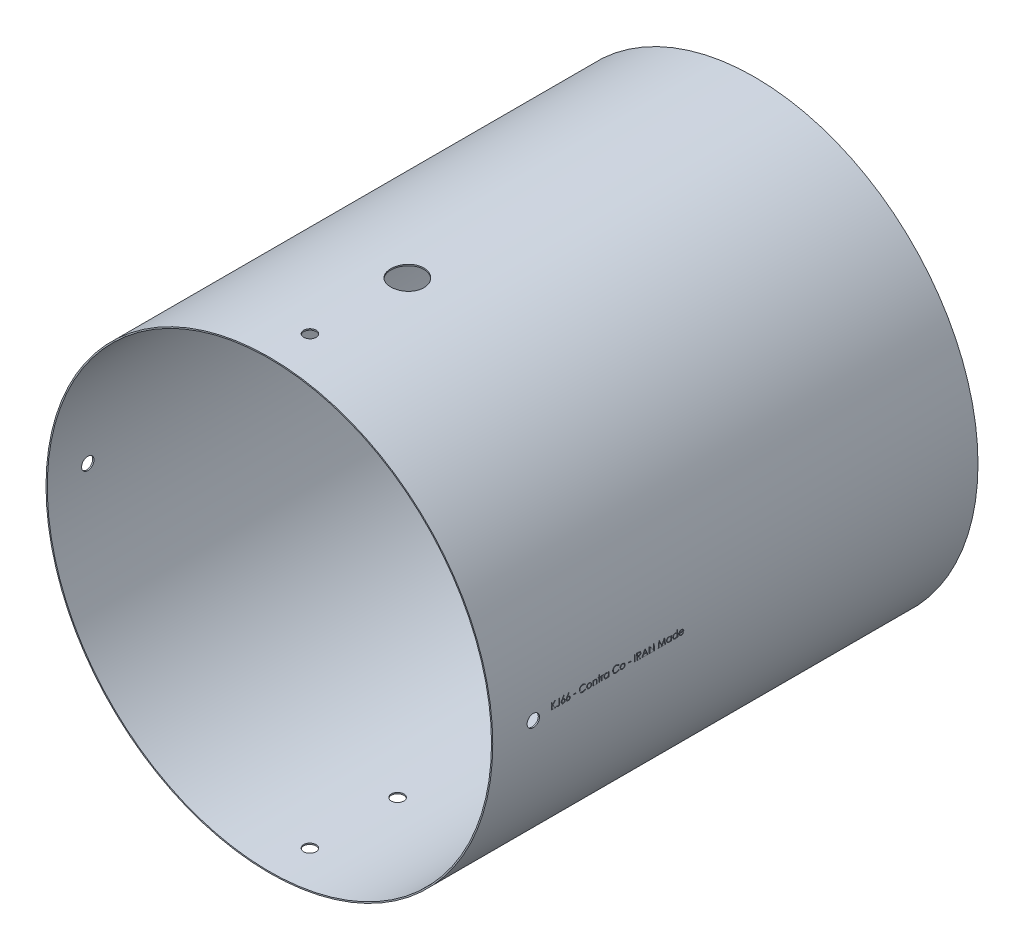
SolidWorks part; units mm, degrees
material "Chrome Stainless Steel"
ref_plane "Front Plane" through (0, 0, 0) normal (0, 0, 1) x (1, 0, 0)
ref_plane "Top Plane" through (0, 0, 0) normal (0, 1, 0) x (1, 0, 0)
ref_plane "Right Plane" through (0, 0, 0) normal (1, 0, 0) x (0, 0, -1)
sketch "Sketch1" plane through (0, 0, 0) normal (0, 1, 0) x (1, 0, 0)
  line L0 (-34.2692, 117.8) -> (-34.2692, 117.5)
  line L1 (-54, 0.4998) -> (-54, 112.5)
  line L2 (-34.2692, 117.5) -> (-53.7, 117.5)
  line L3 (-53.7, 112.5) -> (-53.7, 0.5)
  line L4 (-53.7, 117.5) -> (-53.7, 112.5)
  line L5 (-54, 0.4998) -> (-53.7, 0.5)
  line L6 (0, 0) -> (0, 62.8009) construction
  line L7 (-54, 112.5) -> (-54, 117.8)
  line L8 (-54, 117.8) -> (-34.2692, 117.8)
  point P1 (0, 0)
  point P5 (0, 0)
  point P15 (-54, 117.8)
  point P17 (-34.2692, 117.5)
  point P18 (-34.2692, 117.8)
revolve "Revolve1" add sketch "Sketch1" angle 360 about L6
ref_plane "Plane1" through (53.75, 0, 0) normal (1, 0, 0) x (0, 0, -1)
sketch "Sketch3" plane through (53.75, 0, 0) normal (1, 0, 0) x (0, 0, -1)
  circle A0 centre (10.3, 0) radius 1.5
  point P6 (10.3, 0)
ref_plane "Plane2" through (0, -53.75, 0) normal (0, 1, 0) x (1, 0, 0)
sketch "Sketch5" plane through (0, -53.75, 0) normal (0, 1, 0) x (1, 0, 0)
  circle A0 centre (0, 31.5) radius 1.5
extrude "Cut-Extrude7" cut sketch "Sketch5" along normal blind 10 and the other way blind 20 contours A0
ref_plane "Plane3" through (0, 53.75, 0) normal (0, 1, 0) x (1, 0, 0)
sketch "Sketch6" plane through (0, 53.75, 0) normal (0, 1, 0) x (1, 0, 0)
  circle A2 centre (0, 33.85) radius 4
  point P10 (0, 33.85)
extrude "Cut-Extrude8" cut sketch "Sketch6" against normal blind 13 and the other way blind 14
ref_plane "Plane4" through (54, 0, 0) normal (1, 0, 0) x (0, 0, -1)
extrude "Cut-Extrude11" cut sketch "Sketch3" along normal blind 4 and the other way blind 16
pattern_circular "CirPattern1" count 4 over 360 of "Cut-Extrude11"
ref_plane "Plane5" through (54, 0, 0) normal (1, 0, 0) x (0, 0, -1)
sketch "Sketch7" plane through (54, 0, 0) normal (1, 0, 0) x (0, 0, -1)
  line L0 (14.5347, 0) -> (59.5347, 0) construction
  text T0 "KJ66 - Contra Co - IRAN Made" font "Century Gothic" height in points 6
extrude "Cut-Extrude12" cut sketch "Sketch7" along normal blind 3 and the other way blind 0.2
sketch "Sketch8" plane through (0, 0, -117.8) normal (0, 0, -1) x (-1, 0, 0)
  circle A1 centre (0, 38) radius 1.5
extrude "Cut-Extrude13" cut sketch "Sketch8" against normal blind 10
pattern_circular "CirPattern2" count 12 over 360 about axis through (0, 0, -117.8) along (0, 0, 1) of "Cut-Extrude13"
